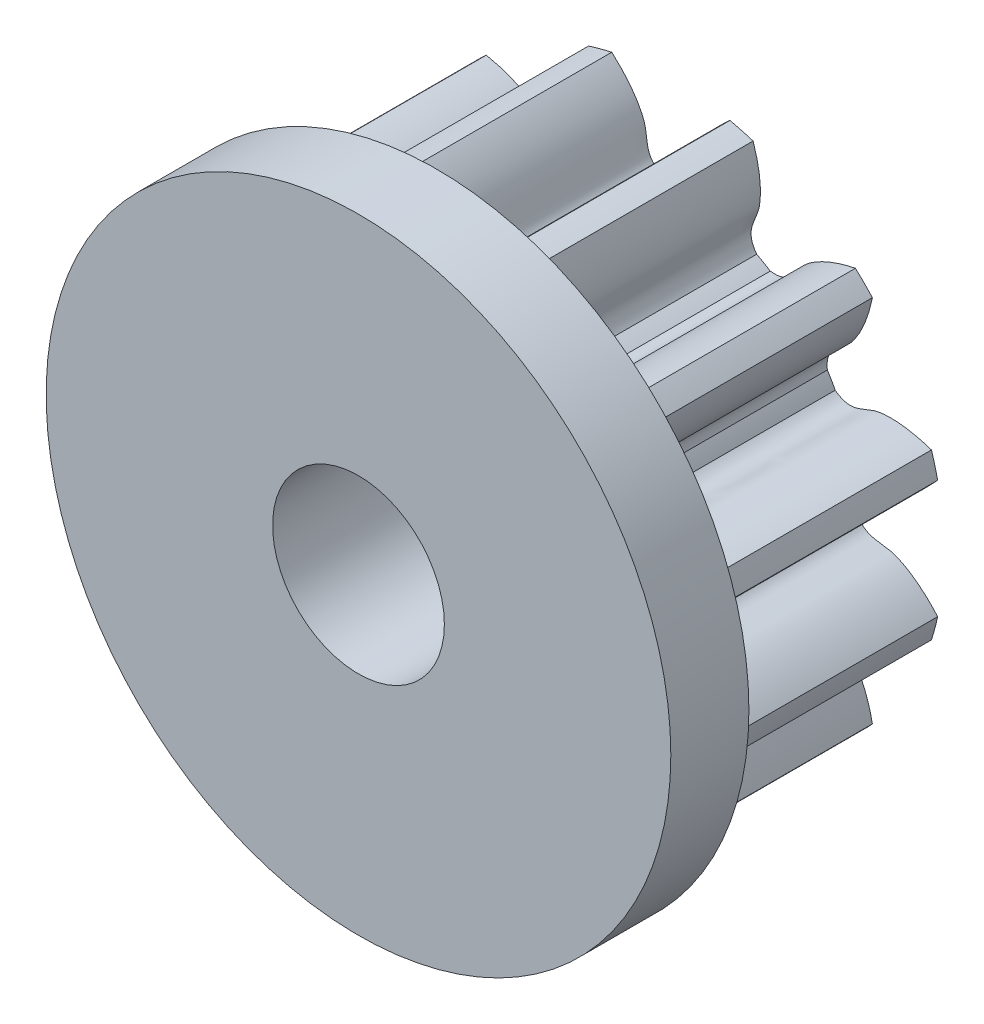
SolidWorks part; units mm, degrees
ref_plane "前视基准面" through (0, 0, 0) normal (0, 0, 1) x (1, 0, 0)
ref_plane "上视基准面" through (0, 0, 0) normal (0, 1, 0) x (1, 0, 0)
ref_plane "右视基准面" through (0, 0, 0) normal (1, 0, 0) x (0, 0, -1)
other "Configuration Table"
sketch "草图1" plane through (0, 0, 0) normal (0, 0, 1) x (1, 0, 0)
  circle A0 centre (0, 0) radius 3.5
extrude "凸台-拉伸1" add sketch "草图1" along normal blind 3
ref_axis "基准轴1" through (0, 0, 3) along (0, 0, -1)
sketch "草图2" plane through (0, 0, 0) normal (0, 0, 1) x (1, 0, 0)
  line L0 (0, 0) -> (0, 3.5) construction
  circle A0 centre (0, 0) radius 3.5 construction
  arc A1 (0.1004, 2.3729) -> (-0.1004, 2.3729) centre (0, 0) ccw
  arc A2 (1.7488, 3.9475) -> (-1.7488, 3.9475) centre (0, 0) ccw
  spline S0 degree 3 poles (0.1004, 2.3729) (0.3404, 2.4747) (0.2872, 2.6724) (0.3381, 2.8447) (0.3413, 2.855) (0.3451, 2.8662) (0.3495, 2.8784) (0.3546, 2.8915) (0.3603, 2.9056) (0.3668, 2.9206) (0.374, 2.9366) (0.3821, 2.9533) (0.3909, 2.971) (0.4007, 2.9894) (0.4114, 3.0086) (0.423, 3.0286) (0.4356, 3.0493) (0.4492, 3.0707) (0.4639, 3.0928) (0.4796, 3.1155) (0.4965, 3.1388) (0.5145, 3.1626) (0.5337, 3.187) (0.554, 3.2119) (0.5756, 3.2372) (0.5985, 3.2629) (0.6226, 3.289) (0.648, 3.3154) (0.6748, 3.342) (0.7028, 3.369) (0.7323, 3.3961) (0.7631, 3.4234) (0.7954, 3.4507) (0.829, 3.4782) (0.8641, 3.5057) (0.9006, 3.5331) (0.9385, 3.5604) (0.978, 3.5877) (1.0189, 3.6147) (1.0613, 3.6416) (1.1052, 3.6681) (1.1506, 3.6944) (1.1975, 3.7203) (1.2459, 3.7457) (1.2958, 3.7707) (1.3472, 3.7952) (1.4001, 3.8191) (1.4546, 3.8424) (1.5105, 3.865) (1.5679, 3.8869) (1.6472, 3.9154) (1.7078, 3.9351) (1.7488, 3.9475) knots 0 0 0 0 0.218015 0.222044 0.226546 0.231522 0.236972 0.242897 0.249295 0.256167 0.263513 0.271332 0.279626 0.288394 0.297636 0.307351 0.317541 0.328204 0.339341 0.350953 0.363038 0.375597 0.38863 0.402137 0.416118 0.430573 0.445502 0.460904 0.476781 0.493132 0.509956 0.527255 0.545027 0.563273 0.581994 0.601188 0.620856 0.640998 0.661614 0.682704 0.704268 0.726305 0.748817 0.771803 0.795262 0.819196 0.843603 0.868484 0.89384 0.919669 0.945972 1 1 1 1
  spline S1 degree 3 poles (-0.1004, 2.3729) (-0.3404, 2.4747) (-0.2872, 2.6724) (-0.3381, 2.8447) (-0.3413, 2.855) (-0.3451, 2.8662) (-0.3495, 2.8784) (-0.3546, 2.8915) (-0.3603, 2.9056) (-0.3668, 2.9206) (-0.374, 2.9366) (-0.3821, 2.9533) (-0.3909, 2.971) (-0.4007, 2.9894) (-0.4114, 3.0086) (-0.423, 3.0286) (-0.4356, 3.0493) (-0.4492, 3.0707) (-0.4639, 3.0928) (-0.4796, 3.1155) (-0.4965, 3.1388) (-0.5145, 3.1626) (-0.5337, 3.187) (-0.554, 3.2119) (-0.5756, 3.2372) (-0.5985, 3.2629) (-0.6226, 3.289) (-0.648, 3.3154) (-0.6748, 3.342) (-0.7028, 3.369) (-0.7323, 3.3961) (-0.7631, 3.4234) (-0.7954, 3.4507) (-0.829, 3.4782) (-0.8641, 3.5057) (-0.9006, 3.5331) (-0.9385, 3.5604) (-0.978, 3.5877) (-1.0189, 3.6147) (-1.0613, 3.6416) (-1.1052, 3.6681) (-1.1506, 3.6944) (-1.1975, 3.7203) (-1.2459, 3.7457) (-1.2958, 3.7707) (-1.3472, 3.7952) (-1.4001, 3.8191) (-1.4546, 3.8424) (-1.5105, 3.865) (-1.5679, 3.8869) (-1.6472, 3.9154) (-1.7078, 3.9351) (-1.7488, 3.9475) knots 0 0 0 0 0.218015 0.222044 0.226546 0.231522 0.236972 0.242897 0.249295 0.256167 0.263513 0.271332 0.279626 0.288394 0.297636 0.307351 0.317541 0.328204 0.339341 0.350953 0.363038 0.375597 0.38863 0.402137 0.416118 0.430573 0.445502 0.460904 0.476781 0.493132 0.509956 0.527255 0.545027 0.563273 0.581994 0.601188 0.620856 0.640998 0.661614 0.682704 0.704268 0.726305 0.748817 0.771803 0.795262 0.819196 0.843603 0.868484 0.89384 0.919669 0.945972 1 1 1 1
extrude "切除-拉伸1" cut sketch "草图2" along normal through all
pattern_circular "阵列(圆周)1" count 12 every 30 about axis through (0, 0, 3) along (0, 0, -1) of "切除-拉伸1"
sketch "草图3" plane through (0, 0, 0) normal (0, 0, 1) x (1, 0, 0)
  circle A0 centre (0, 0) radius 3 construction
  dimension "Dn" = 6
sketch "草图5" plane through (0, 0, 3) normal (0, 0, 1) x (1, 0, 0)
  circle A0 centre (0, 0) radius 4
  circle A1 centre (0, 0) radius 4 construction
extrude "凸台-拉伸2" add sketch "草图5" along normal blind 1
sketch "草图6" plane through (0, 0, 4) normal (0, 0, 1) x (1, 0, 0)
  circle A0 centre (0, 0) radius 1.1
  circle A1 centre (0, 0) radius 1.1 construction
extrude "切除-拉伸2" cut sketch "草图6" against normal blind 10
